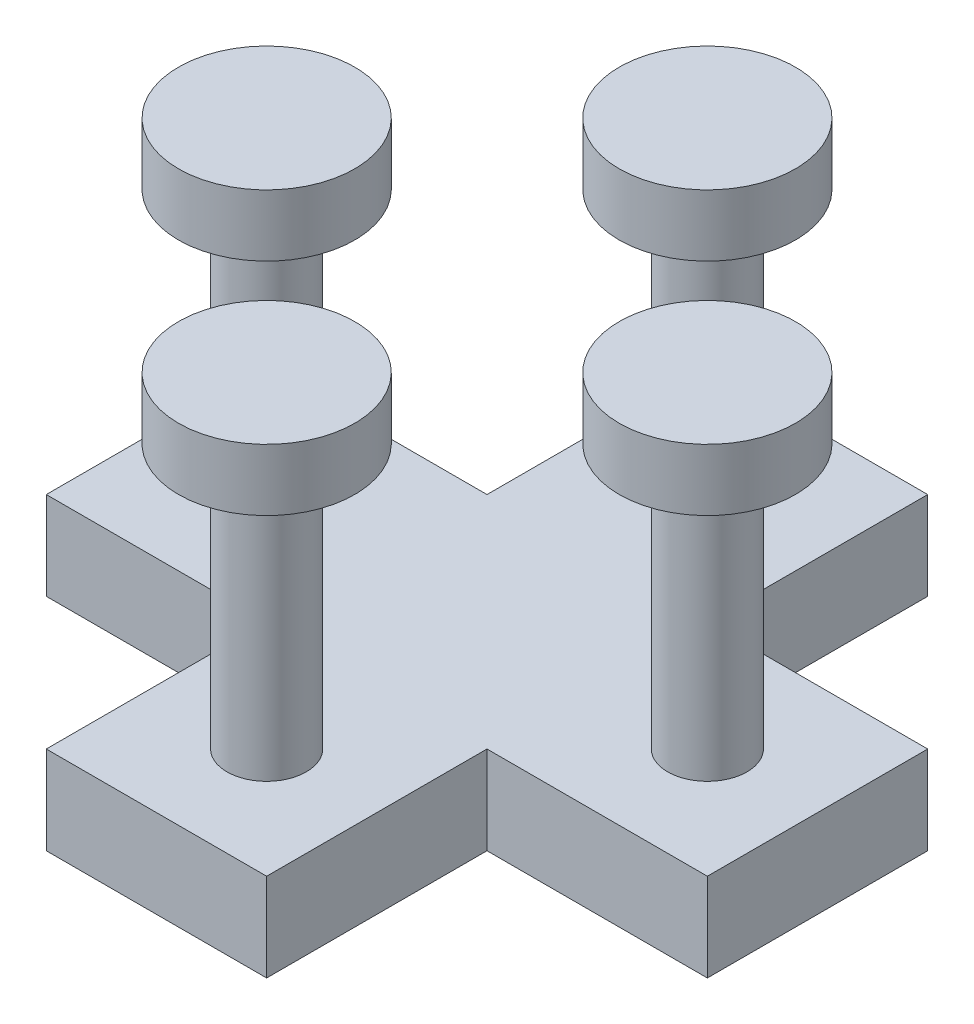
SolidWorks part; units mm, degrees
ref_plane "Front Plane" through (0, 0, 0) normal (0, 0, 1) x (1, 0, 0)
ref_plane "Top Plane" through (0, 0, 0) normal (0, 1, 0) x (1, 0, 0)
ref_plane "Right Plane" through (0, 0, 0) normal (1, 0, 0) x (0, 0, -1)
sketch "Sketch1" plane through (0, 0, 0) normal (0, 1, 0) x (1, 0, 0)
  line L0 (-8.3487, -10.4521) -> (-8.3487, -4.1021)
  line L1 (-8.3487, -4.1021) -> (-1.9987, -4.1021)
  line L2 (-1.9987, -4.1021) -> (-1.9987, -10.4521)
  line L3 (-1.9987, -10.4521) -> (4.3513, -10.4521)
  line L4 (4.3513, -10.4521) -> (4.3513, -16.8021)
  line L5 (4.3513, -16.8021) -> (-1.9987, -16.8021)
  line L6 (-1.9987, -16.8021) -> (-1.9987, -23.1521)
  line L7 (-1.9987, -23.1521) -> (-8.3487, -23.1521)
  line L8 (-8.3487, -23.1521) -> (-8.3487, -16.8021)
  line L9 (-8.3487, -16.8021) -> (-14.6987, -16.8021)
  line L10 (-14.6987, -16.8021) -> (-14.6987, -10.4521)
  line L11 (-14.6987, -10.4521) -> (-8.3487, -10.4521)
  dimension "D1" = 6.35
  dimension "D2" = 6.35
  dimension "D3" = 6.35
  dimension "D4" = 6.35
  dimension "D5" = 6.35
  dimension "D6" = 6.35
  dimension "D7" = 6.35
  dimension "D8" = 6.35
  dimension "D9" = 6.35
  dimension "D10" = 6.35
extrude "body" add sketch "Sketch1" along normal blind 2.54
sketch "Sketch2" plane through (0, 2.54, 0) normal (0, 1, 0) x (1, 0, 0)
  line L0 (-8.3487, -10.4521) -> (-14.6987, -10.4521) construction
  line L1 (-1.9987, -23.1521) -> (-1.9987, -16.8021) construction
  line L2 (-1.9987, -16.8021) -> (4.3513, -16.8021) construction
  line L3 (-1.9987, -10.4521) -> (-1.9987, -4.1021) construction
  line L4 (-1.9987, -4.1021) -> (-8.3487, -4.1021) construction
  line L5 (-14.6987, -10.4521) -> (-14.6987, -16.8021) construction
  line L6 (-8.3487, -23.1521) -> (-1.9987, -23.1521) construction
  line L7 (4.3513, -16.8021) -> (4.3513, -10.4521) construction
  circle A0 centre (-5.1737, -7.2771) radius 1.143
  circle A1 centre (1.1763, -13.6271) radius 1.143
  circle A2 centre (-5.1737, -19.9771) radius 1.143
  circle A3 centre (-11.5237, -13.6271) radius 1.143
  dimension "D1" = 2.286
  dimension "D2" = 2.286
  dimension "D3" = 2.286
  dimension "D4" = 2.286
  dimension "D5" = 3.175
  dimension "D6" = 3.175
  dimension "D7" = 3.175
  dimension "D8" = 3.175
  dimension "D9" = 3.175
  dimension "D10" = 3.175
  dimension "D11" = 3.175
  dimension "D12" = 3.175
extrude "pegs" add sketch "Sketch2" along normal blind 7.62
ref_point "centre 1"
ref_point "centre 2"
ref_point "centre 3"
ref_point "centre 4"
ref_plane "plane o' feet" through (0, 10.16, 0) normal (0, 1, 0) x (1, 0, 0)
sketch "Sketch3" plane through (0, 10.16, 0) normal (0, 1, 0) x (1, 0, 0)
  circle A0 centre (-5.1737, -7.2771) radius 2.54
  circle A1 centre (-11.5237, -13.6271) radius 2.54
  circle A2 centre (-5.1737, -19.9771) radius 2.54
  circle A3 centre (1.1763, -13.6271) radius 2.54
  dimension "D1" = 5.08
  dimension "D2" = 5.08
  dimension "D3" = 5.08
  dimension "D4" = 5.08
extrude "feet" add sketch "Sketch3" along normal blind 1.778
